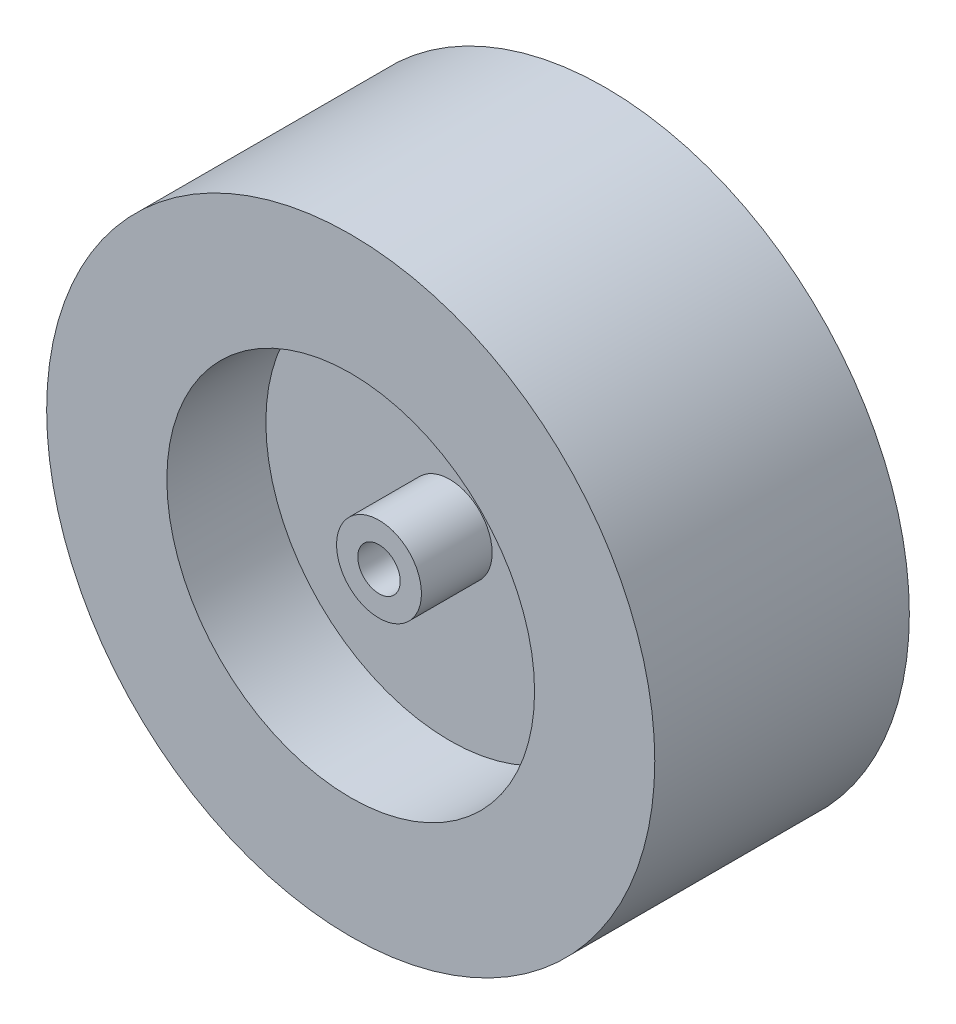
SolidWorks part; units mm, degrees
ref_plane "Front Plane" through (0, 0, 0) normal (0, 0, 1) x (1, 0, 0)
ref_plane "Top Plane" through (0, 0, 0) normal (0, 1, 0) x (1, 0, 0)
ref_plane "Right Plane" through (0, 0, 0) normal (1, 0, 0) x (0, 0, -1)
sketch "Sketch1" plane through (0, 0, 0) normal (0, 0, 1) x (1, 0, 0)
  circle A0 centre (0, 0) radius 1.5
  circle A1 centre (0, 0) radius 13
  circle A2 centre (0, 0) radius 21.5
  circle A3 centre (0, 0) radius 3
  dimension "D1" = 26
  dimension "D2" = 3
  dimension "D3" = 43
  dimension "D4" = 6
extrude "Boss-Extrude7" add sketch "Sketch1" along normal blind 7 and the other way blind 3 contours A3 | A0
extrude "Boss-Extrude8" add sketch "Sketch1<10>" along normal mid plane 18 separate body contours A2 A1 region at (-20.8919, 0, 0)
sketch "Sketch1<10>" plane through (0, 0, 0) normal (0, 0, 1) x (1, 0, 0) same geometry as "Sketch1"
extrude "Boss-Extrude9" add sketch "Sketch1<11>" along normal mid plane 4 contours A1 A3 region at (-12.6323, 0, 0)
sketch "Sketch1<11>" plane through (0, 0, 0) normal (0, 0, 1) x (1, 0, 0) same geometry as "Sketch1"
